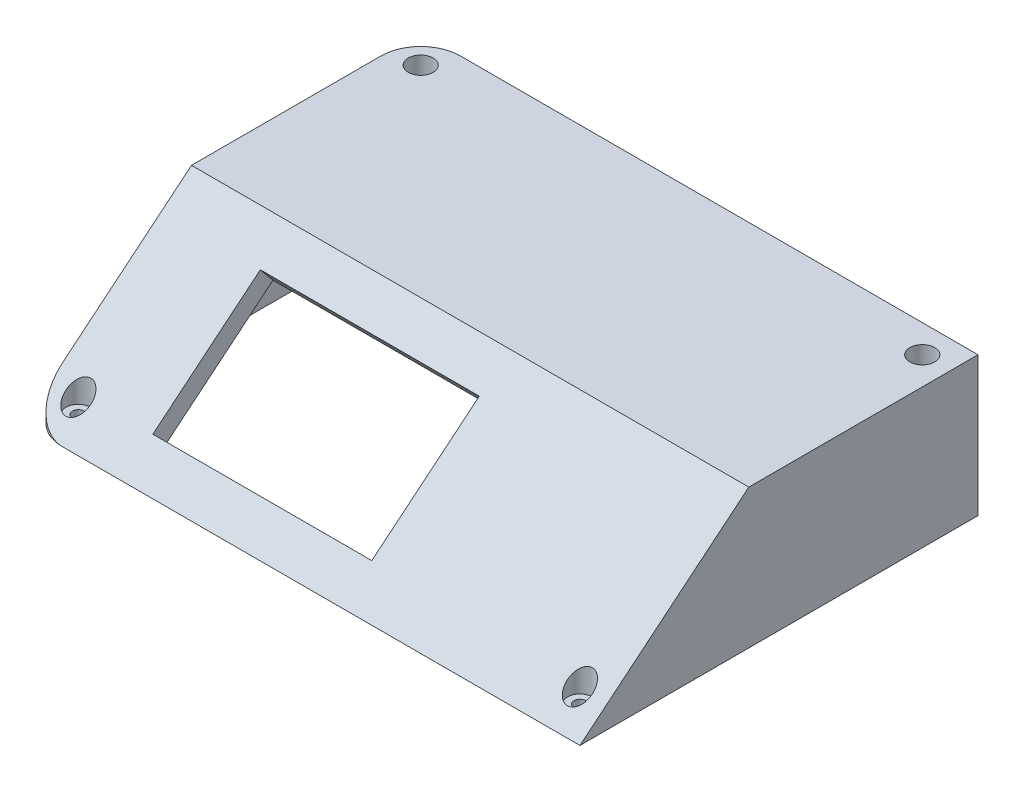
SolidWorks part; units mm, degrees
material "Custom Plastic"
ref_plane "Front Plane" through (0, 0, 0) normal (0, 0, 1) x (1, 0, 0)
ref_plane "Top Plane" through (0, 0, 0) normal (0, 1, 0) x (1, 0, 0)
ref_plane "Right Plane" through (0, 0, 0) normal (1, 0, 0) x (0, 0, -1)
sketch "Sketch2" plane through (0, 0, 0) normal (1, 0, 0) x (0, 0, -1)
  line L0 (-28.7868, 17.5) -> (-71.2132, -17.5)
  line L1 (-28.7868, -17.5) -> (28.7868, -17.5)
  line L2 (-28.7868, -17.5) -> (-28.7868, 17.5)
  line L3 (-28.7868, 17.5) -> (28.7868, 17.5)
  line L4 (28.7868, -17.5) -> (28.7868, 17.5)
  line L5 (-28.7868, -17.5) -> (28.7868, 17.5) construction
  line L6 (-28.7868, 17.5) -> (28.7868, -17.5) construction
  line L7 (-71.2132, -17.5) -> (-28.7868, -17.5)
  line L8 (-26.9906, 12.5) -> (-63.3561, -17.5)
  line L9 (-26.9906, 12.5) -> (23.7868, 12.5)
  line L10 (23.7868, 12.5) -> (23.7868, -17.5)
  point P0 (0, 0)
  dimension "D1" = 55
  dimension "D2" = 100
  dimension "D3" = 35
  dimension "D4" = 5
  dimension "D5" = 5
  dimension "D6" = 5
extrude "Boss-Extrude1" add sketch "Sketch2" against normal blind 140 contours L0 L7 L2 | L1 L4 L3 L2 | L10 L9 L8 L2 L1 | L2 L8 L7 region at (0, -1.5653, 48.1025) region at (0, 16.8262, 0) region at (0, -2.5123, 2.4783) region at (0, -7.9939, 40.3099)
ref_plane "Plane1" through (-70, 0, 0) normal (-1, 0, 0) x (0, 0, 1)
sketch "Sketch3" plane through (-70, 0, 0) normal (-1, 0, 0) x (0, 0, 1)
  line L0 (-23.7868, -17.5) -> (-23.7868, 12.5)
  line L1 (71.2132, -17.5) -> (-28.7868, -17.5) construction
  line L2 (-23.7868, 12.5) -> (26.9906, 12.5)
  line L3 (26.9906, 12.5) -> (63.3561, -17.5)
  line L4 (63.3561, -17.5) -> (-23.7868, -17.5)
  line L5 (28.7868, 17.5) -> (71.2132, -17.5) construction
  line L6 (-28.7868, -17.5) -> (-28.7868, 17.5) construction
  line L7 (28.7868, 17.5) -> (-28.7868, 17.5) construction
  dimension "D1" = 5
  dimension "D2" = 5
  dimension "D3" = 5
extrude "Cut-Extrude1" cut sketch "Sketch3" against normal offset from surface 5 and the other way offset from surface 5 up to face at (0, 0, 10.6066) other way up to face at (-140, 0, 10.6066)
sketch "Sketch4" plane through (0, 24.5442, 20.2479) normal (0, 0.7714, 0.6364) x (1, 0, 0)
  line L0 (-140, -11.0695) -> (-140, -66.0695) construction
  line L1 (-115, -56.0695) -> (-60, -56.0695)
  line L2 (-115, -56.0695) -> (-115, -21.0695)
  line L3 (-115, -21.0695) -> (-60, -21.0695)
  line L4 (-60, -56.0695) -> (-60, -21.0695)
  line L5 (-115, -56.0695) -> (-60, -21.0695) construction
  line L6 (-115, -21.0695) -> (-60, -56.0695) construction
  point P0 (-87.5, -38.5695)
  point P10 (-140, -38.5695)
  dimension "D1" = 35
  dimension "D2" = 25
  dimension "D3" = 55
extrude "Cut-Extrude2" cut sketch "Sketch4" against normal up to surface (5 mm away) up to face at (-70, -2.5, 45.1733)
sketch "Sketch6" plane through (0, -17.5, 0) normal (0, -1, 0) x (1, 0, 0)
  line L0 (-140, 71.2132) -> (0, 71.2132) construction
  line L2 (-140, 71.2132) -> (-140, -28.7868) construction
  line L4 (-140, -28.7868) -> (0, -28.7868) construction
  line L5 (-140, 61.2132) -> (-140, 71.2132)
  line L6 (-140, 71.2132) -> (-130, 71.2132)
  line L7 (-140, -18.7868) -> (-140, -28.7868)
  line L8 (-140, -28.7868) -> (-130, -28.7868)
  arc A0 (-140, 61.2132) -> (-130, 71.2132) centre (-130, 61.2132) cw
  arc A1 (-140, -18.7868) -> (-130, -28.7868) centre (-130, -18.7868) ccw
  dimension "D1" = 10
  dimension "D4" = 10
  dimension "D2" = 10
  dimension "D3" = 10
  dimension "D5" = 10
  dimension "D6" = 10
extrude "Cut-Extrude3" cut sketch "Sketch6" against normal through all
sketch "Sketch8" plane through (0, -17.5, 0) normal (0, -1, 0) x (1, 0, 0)
  line L0 (-135, 63.3561) -> (-135, -23.7868) construction
  line L1 (-135, 53.3561) -> (-125, 53.3561)
  line L2 (-135, 53.3561) -> (-135, 63.3561)
  line L3 (-135, 63.3561) -> (-125, 63.3561)
  line L4 (-125, 53.3561) -> (-125, 63.3561)
  line L5 (-5, 63.3561) -> (-135, 63.3561) construction
  line L6 (-135, 19.7846) -> (-5, 19.7846) construction
  line L7 (-70, -28.7868) -> (-70, 71.2132) construction
  line L8 (-130, -28.7868) -> (0, -28.7868) construction
  line L9 (-130, 71.2132) -> (0, 71.2132) construction
  line L12 (-15, 53.3561) -> (-15, 63.3561)
  line L13 (-5, 63.3561) -> (-15, 63.3561)
  line L14 (-5, 53.3561) -> (-5, 63.3561)
  line L15 (-5, 53.3561) -> (-15, 53.3561)
  line L17 (-5, -23.7868) -> (-5, 63.3561) construction
  line L18 (-5, -13.7868) -> (-15, -13.7868)
  line L19 (-5, -13.7868) -> (-5, -23.7868)
  line L20 (-5, -23.7868) -> (-15, -23.7868)
  line L21 (-15, -13.7868) -> (-15, -23.7868)
  line L22 (-125, -13.7868) -> (-125, -23.7868)
  line L23 (-135, -23.7868) -> (-125, -23.7868)
  line L24 (-135, -13.7868) -> (-135, -23.7868)
  line L25 (-135, -13.7868) -> (-125, -13.7868)
  point P20 (-70, 19.7846)
  line M13 (-5, 63.3561) -> (-5, -23.7868)
  line M14 (-5, -23.7868) -> (-135, -23.7868)
  line M15 (-135, -23.7868) -> (-135, 63.3561)
  line M16 (-135, 63.3561) -> (-5, 63.3561)
  dimension "D1" = 10
  dimension "D2" = 10
extrude "Boss-Extrude2" add sketch "Sketch8" against normal up to surface (8.2496 mm away) contours L1 L4 M16 M15 | L15 L12 M13 M16 region at (-130, -17.5, 58.3561) region at (-10, -17.5, 58.3561) up to face at (-87.5, -3.8569, 46.8182)
extrude "Boss-Extrude3" add sketch "Sketch8<3>" against normal up to surface (30 mm away) contours L25 L22 M15 M14 | L18 L21 M14 M13 region at (-10, -17.5, -18.7868) region at (-130, -17.5, -18.7868) up to face at (-70, 12.5, 1.6019)
sketch "Sketch8<3>" plane through (0, -17.5, 0) normal (0, -1, 0) x (1, 0, 0) same geometry as "Sketch8"
sketch "Sketch7" plane through (0, 17.5, 0) normal (0, 1, 0) x (1, 0, 0)
  line L0 (-140, 18.7868) -> (-140, 28.7868)
  line L1 (-140, -61.2132) -> (-140, 18.7868) construction
  line L2 (-140, -21.2132) -> (0, -21.2132) construction
  line L3 (-140, 28.7868) -> (-130, 28.7868)
  line L4 (0, 28.7868) -> (-10, 28.7868)
  line L5 (-70, -71.2132) -> (-70, 28.7868) construction
  line L6 (0, 18.7868) -> (0, 28.7868)
  line L7 (-130, 28.7868) -> (0, 28.7868) construction
  line L8 (-130, -71.2132) -> (0, -71.2132) construction
  line L9 (-140, -28.7868) -> (-140, 18.7868) construction
  line L10 (0, -28.7868) -> (0, 28.7868) construction
  line L11 (0, -61.2132) -> (0, -71.2132)
  line L12 (0, -71.2132) -> (-10, -71.2132)
  line L13 (-140, -71.2132) -> (-130, -71.2132)
  line L14 (-140, -61.2132) -> (-140, -71.2132)
  arc A0 (-140, 18.7868) -> (-130, 28.7868) centre (-133, 21.7868) ccw
  arc A1 (-130, 28.7868) -> (-140, 18.7868) centre (-130, 18.7868) ccw construction
  arc A2 (0, 18.7868) -> (-10, 28.7868) centre (-7, 21.7868) cw
  arc A3 (0, -61.2132) -> (-10, -71.2132) centre (-7, -64.2132) ccw
  arc A4 (-140, -61.2132) -> (-130, -71.2132) centre (-133, -64.2132) cw
  circle A5 centre (-133, 21.7868) radius 3.125
  circle A6 centre (-7, 21.7868) radius 3.125
  circle A7 centre (-7, -64.2132) radius 3.125
  circle A8 centre (-133, -64.2132) radius 3.125
  circle A9 centre (-133, 21.7868) radius 1.5
  circle A10 centre (-7, 21.7868) radius 1.5
  circle A11 centre (-133, -64.2132) radius 1.5
  circle A12 centre (-7, -64.2132) radius 1.5
  point P8 (-70, -21.2132)
  point P25 (-70, -21.2132)
  point P45 (0, 0)
  dimension "D2" = 6.25
  dimension "D3" = 3
  dimension "D1" = 7
extrude "Cut-Extrude5" cut sketch "Sketch7" against normal offset from surface (33 mm away) 2 contours A8 | A5 | A6 | A7 region at (-136.0366, 17.5, -21.7868) region at (-10.0366, 17.5, -21.7868) region at (-10.0366, 17.5, 64.2132) region at (-136.0366, 17.5, 64.2132) up to face at (-70, -17.5, 19.7846)
extrude "Cut-Extrude6" cut sketch "Sketch7<4>" against normal up to surface (35 mm away) contours A11 | A9 | A10 | A12 region at (-133, 17.5, -21.7868) region at (-7, 17.5, -21.7868) region at (-133, 17.5, 64.2132) region at (-7, 17.5, 64.2132) up to face at (-70, -17.5, 19.7846)
sketch "Sketch7<4>" plane through (0, 17.5, 0) normal (0, 1, 0) x (1, 0, 0) same geometry as "Sketch7"
equation "\"device_width\"=100"
equation "\"D2@Sketch2\"=\"device_width\""
equation "\"cap_height\"=35"
equation "\"D3@Sketch2\"=\"cap_height\""
equation "\"slant_length\"=55"
equation "\"D1@Sketch2\"=\"slant_length\""
equation "\"cap_length\" = 140"
equation "\"D1@Boss-Extrude1\"=\"cap_length\""
equation "\"device_wall\"=5"
equation "\"D1@Sketch3\"=\"device_wall\""
equation "\"D2@Sketch3\"=\"device_wall\""
equation "\"D3@Sketch3\"=\"device_wall\""
equation "\"D1@Cut-Extrude1\"=\"device_wall\""
equation "\"D2@Cut-Extrude1\"=\"device_wall\""
